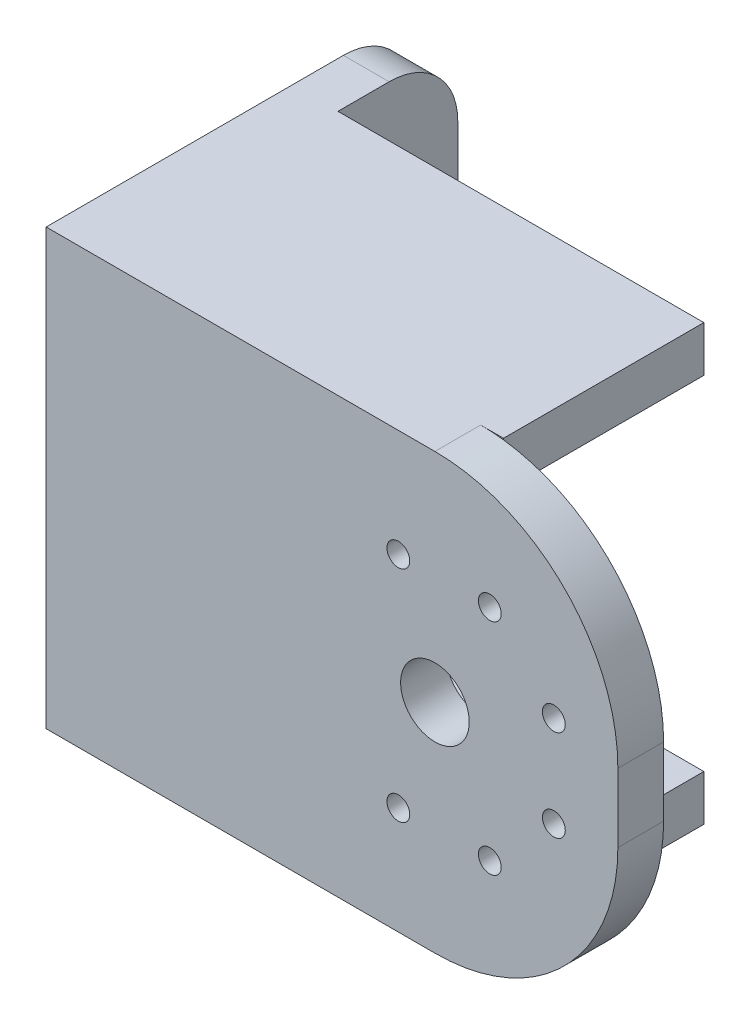
SolidWorks part; units mm, degrees
ref_plane "Front Plane" through (0, 0, 0) normal (0, 0, 1) x (1, 0, 0)
ref_plane "Top Plane" through (0, 0, 0) normal (0, 1, 0) x (1, 0, 0)
ref_plane "Right Plane" through (0, 0, 0) normal (1, 0, 0) x (0, 0, -1)
sketch "Sketch3" plane through (0, 0, 0) normal (0, 0, 1) x (1, 0, 0)
  line L6 (68.6171, 80.0599) -> (153.6171, 80.0599)
  line L10 (68.6171, 80.0599) -> (68.6171, -14.9401)
  line L36 (-101.4371, 49.8561) -> (-17.2351, 49.8561) construction
  line L70 (68.6171, -14.9401) -> (153.6171, -14.9401)
  line L71 (193.6171, 40.0599) -> (193.6171, 25.0599)
  circle A22 centre (153.6171, 32.5599) radius 7.5
  circle A23 centre (179.6171, 42.5599) radius 2.5
  circle A24 centre (145.6171, 56.5599) radius 2.5
  circle A25 centre (165.6171, 56.5599) radius 2.5
  circle A26 centre (145.6171, 8.5599) radius 2.5
  circle A27 centre (165.6171, 8.5599) radius 2.5
  circle A28 centre (179.6171, 22.5599) radius 2.5
  arc A29 (153.6171, -14.9401) -> (193.6171, 25.0599) centre (153.6171, 25.0599) ccw
  arc A30 (153.6171, 80.0599) -> (193.6171, 40.0599) centre (153.6171, 40.0599) cw
  point P23 (193.6171, 80.0599)
  dimension "D2" = 5
  dimension "D3" = 10
  dimension "D4" = 26
  dimension "D7" = 5
  dimension "D21" = 125
  dimension "D22" = 40
  dimension "D23" = 47.5
  dimension "D1" = 15
  dimension "D5" = 5
  dimension "D6" = 5
  dimension "D8" = 5
  dimension "D9" = 5
  dimension "D24" = 40
  dimension "D10" = 8
  dimension "D11" = 24
  dimension "D12" = 20
  dimension "D15" = 20
  dimension "D16" = 8
  dimension "D17" = 20
  dimension "D18" = 48
  dimension "D19" = 48
  dimension "D20" = 95
  dimension "D13" = 26
  dimension "D14" = 24
extrude "Boss-Extrude1" add sketch "Sketch3" along normal blind 10
sketch "Sketch4" plane through (0, 0, 0) normal (0, 0, -1) x (-1, 0, 0)
  line L0 (-68.6171, -14.9401) -> (-153.6171, -14.9401) construction
  line L1 (-68.6171, 80.0599) -> (-78.6171, 80.0599)
  line L2 (-68.6171, 80.0599) -> (-68.6171, -14.9401)
  line L3 (-68.6171, -14.9401) -> (-78.6171, -14.9401)
  line L4 (-78.6171, 80.0599) -> (-78.6171, -14.9401)
  dimension "D1" = 10
extrude "Boss-Extrude2" add sketch "Sketch4" along normal blind 70
sketch "Sketch5" plane through (0, 0, 0) normal (0, 0, -1) x (-1, 0, 0)
  line L1 (-78.6171, 80.0599) -> (-158.6171, 80.0599)
  line L2 (-78.6171, 80.0599) -> (-78.6171, 70.0599)
  line L3 (-78.6171, 70.0599) -> (-158.6171, 70.0599)
  line L4 (-158.6171, 80.0599) -> (-158.6171, 70.0599)
  line L5 (-78.6171, -14.9401) -> (-158.6171, -14.9401)
  line L6 (-78.6171, -14.9401) -> (-78.6171, -4.9401)
  line L7 (-78.6171, -4.9401) -> (-158.6171, -4.9401)
  line L8 (-158.6171, -14.9401) -> (-158.6171, -4.9401)
  dimension "D1" = 10
  dimension "D2" = 10
  dimension "D3" = 80
  dimension "D4" = 80
extrude "Boss-Extrude3" add sketch "Sketch5" along normal blind 43.8
sketch "Sketch6" plane through (0, -14.9401, 0) normal (0, -1, 0) x (1, 0, 0)
  line L0 (52.25, 0) -> (-52.25, 0) construction
  line L1 (78.6171, 0) -> (110.6171, 0)
  line L2 (78.6171, 0) -> (78.6171, -36)
  line L3 (78.6171, -36) -> (110.6171, -36)
  line L4 (110.6171, 0) -> (110.6171, -36)
  line L5 (68.6171, 10) -> (68.6171, -70) construction
  dimension "D1" = 10
  dimension "D2" = 36
  dimension "D3" = 32
extrude "Cut-Extrude1" cut sketch "Sketch6" against normal blind 43.8
fillet "Fillet2" radius 15 2 edges at (73.6171, 80.0599, -70) (73.6171, -14.9401, -70)
sketch "Sketch8" plane through (68.6171, 0, 0) normal (-1, 0, 0) x (0, 0, 1)
  line L0 (10, 80.0599) -> (-55, 80.0599) construction
  line L1 (-40, 32.5599) -> (-56.1679, 25.863) construction
  line L2 (-70, 32.5599) -> (0, 32.5599) construction
  line L3 (-70, 0.0599) -> (-70, 65.0599) construction
  circle A0 centre (-40, 32.5599) radius 7.5
  circle A1 centre (-56.1679, 25.863) radius 2.5
  circle A2 centre (-56.1679, 39.2569) radius 2.5
  circle A3 centre (-46.697, 48.7278) radius 2.5
  circle A4 centre (-33.303, 48.7278) radius 2.5
  circle A5 centre (-23.8321, 39.2569) radius 2.5
  circle A6 centre (-23.8321, 25.863) radius 2.5
  circle A7 centre (-33.303, 16.392) radius 2.5
  circle A8 centre (-46.697, 16.392) radius 2.5
  point P10 (0, 0)
  point P27 (-40, 32.5599)
  dimension "D1" = 15
  dimension "D6" = 5
  dimension "D2" = 47.5
  dimension "D3" = 30
  dimension "D4" = 17.5
  dimension "D5" = 22.5
  dimension "D7" = 8
extrude "Cut-Extrude2" cut sketch "Sketch8" against normal blind 43.8
